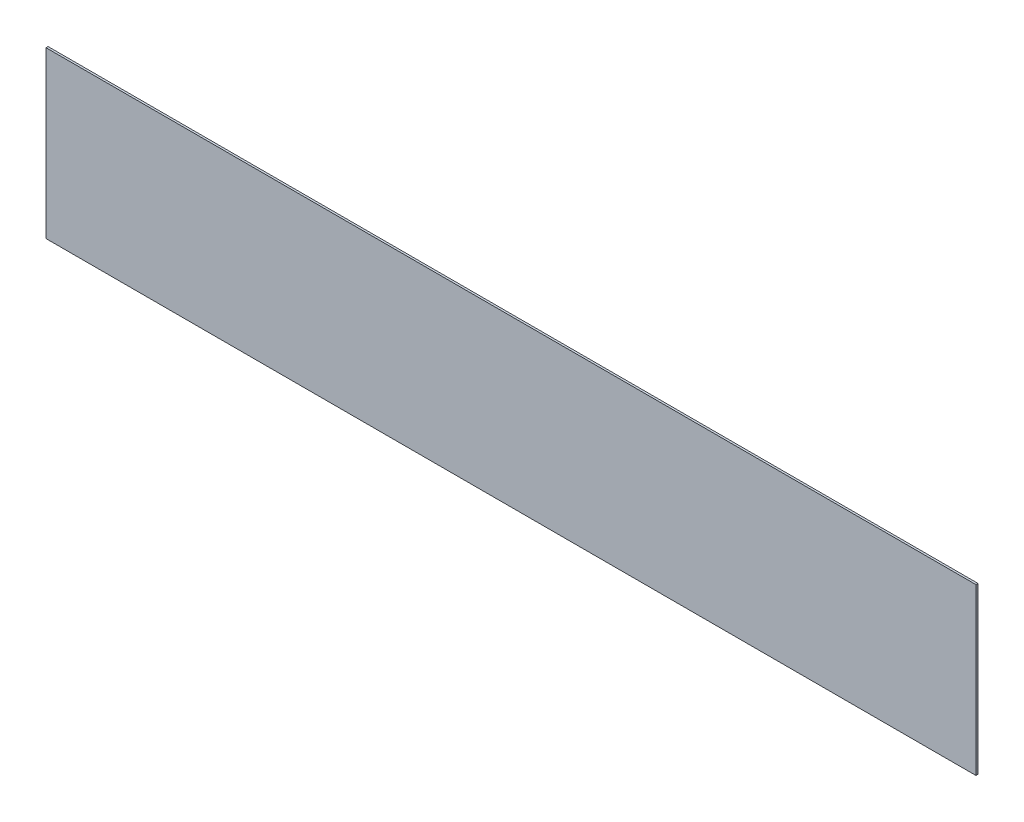
SolidWorks part; units mm, degrees
material "1345 Alloy"
ref_plane "Front Plane" through (0, 0, 0) normal (0, 0, 1) x (1, 0, 0)
ref_plane "Top Plane" through (0, 0, 0) normal (0, 1, 0) x (1, 0, 0)
ref_plane "Right Plane" through (0, 0, 0) normal (1, 0, 0) x (0, 0, -1)
sketch "Sketch1" plane through (0, 0, 0) normal (0, 0, 1) x (1, 0, 0)
  line L1 (-225, 40) -> (225, 40)
  line L2 (-225, 40) -> (-225, -40)
  line L3 (-225, -40) -> (225, -40)
  line L4 (225, 40) -> (225, -40)
  line L5 (-225, 40) -> (225, -40) construction
  line L6 (-225, -40) -> (225, 40) construction
  point P0 (0, 0)
  dimension "D1" = 450
  dimension "D2" = 80
extrude "Boss-Extrude1" add sketch "Sketch1" along normal blind 1
